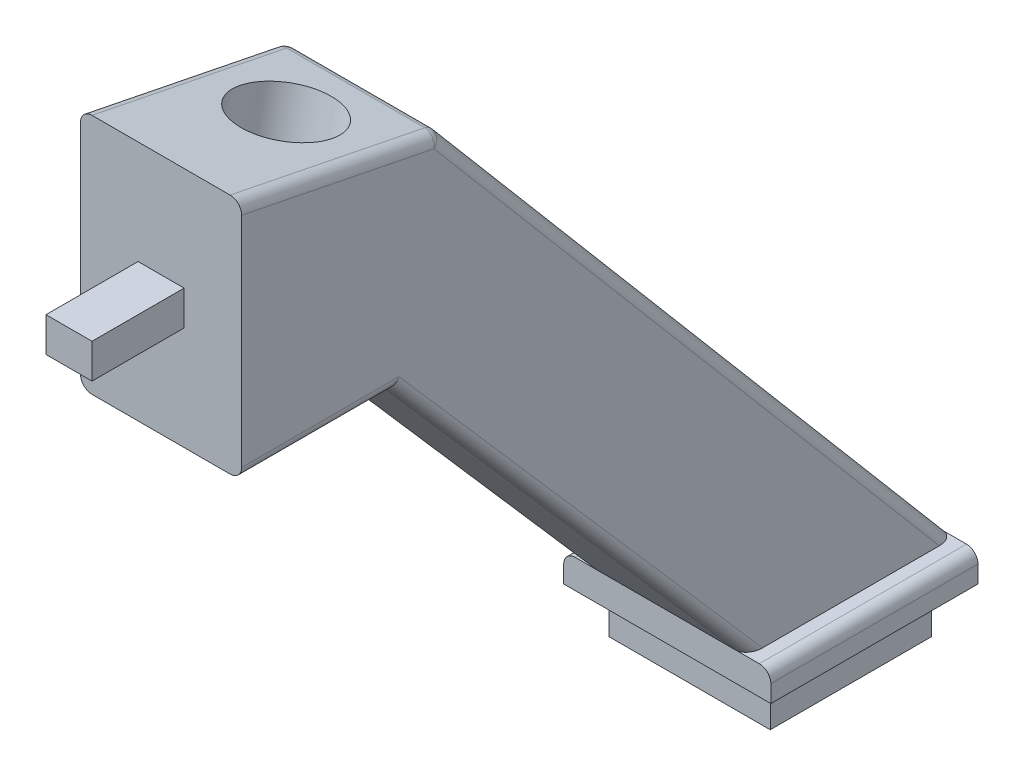
SolidWorks part; units mm, degrees
ref_plane "Front Plane" through (0, 0, 0) normal (0, 0, 1) x (1, 0, 0)
ref_plane "Top Plane" through (0, 0, 0) normal (0, 1, 0) x (1, 0, 0)
ref_plane "Right Plane" through (0, 0, 0) normal (1, 0, 0) x (0, 0, -1)
sketch "Sketch2" plane through (0, 0, 0) normal (0, 1, 0) x (1, 0, 0)
  line L2 (7, 7) -> (-7, 7)
  line L3 (-7, 7) -> (-7, -7)
  line L4 (-7, -7) -> (7, -7)
  line L5 (7, -7) -> (7, 7)
  point P4 (0, 0)
  point P8 (0, 0)
  point P11 (0, 7)
extrude "Boss-Extrude1" add sketch "Sketch2" against normal blind 4 and the other way blind 2.5
sketch "Sketch7" plane through (0, 0, 0) normal (0, 0, 1) x (1, 0, 0)
  line L0 (-6.0346, 0) -> (-4.0346, 0)
  line L2 (0, -33.0044) -> (0, 33.0044) construction
  line L3 (-6.0346, 0) -> (-6.0346, -0.5)
  line L8 (-6.0346, -0.5) -> (-4.0346, -0.5)
  line L9 (-4.0346, -0.5) -> (-4.0346, 0)
  line L10 (4.0346, -0.5) -> (4.0346, 0)
  line L11 (6.0346, -0.5) -> (4.0346, -0.5)
  line L12 (6.0346, 0) -> (6.0346, -0.5)
  line L13 (6.0346, 0) -> (4.0346, 0)
  dimension "D1" = 2
  dimension "D2" = 0.5
sketch "Sketch11" plane through (0, 0, 0) normal (0, 1, 0) x (1, 0, 0)
  line L0 (-8.9488, -8.9993) -> (-8.9488, 9.0007)
  line L1 (-8.9488, 9.0007) -> (9.0512, 9.0007)
  line L2 (-8.9488, -8.9993) -> (9.0512, -8.9993)
  line L3 (9.0512, -8.9993) -> (9.0512, 9.0007)
  dimension "D1" = 18
  dimension "D2" = 18
extrude "Boss-Extrude4" add sketch "Sketch11" along normal blind 2.5
sketch "Sketch3" plane through (0, 0, 0) normal (0, 1, 0) x (1, 0, 0)
  line L0 (2.98, 3.0412) -> (2.98, -2.9588)
  line L2 (2.98, 3.0412) -> (-3.02, 3.0412)
  line L3 (-3.02, 3.0412) -> (-3.02, -2.9588)
  line L4 (-3.02, -2.9588) -> (2.98, -2.9588)
  dimension "D1" = 6
  dimension "D2" = 6
extrude "Cut-Extrude5" cut sketch "Sketch3" against normal blind 4 and the other way blind 4
sketch "Sketch13" plane through (0, 0, 0) normal (1, 0, 0) x (0, 0, -1)
  line L1 (-39.7149, 37.7068) -> (-52.9339, 37.7068)
  line L2 (0, 0) -> (0, 2.5)
  line L3 (0, 2.5) -> (-9, 2.5)
  line L4 (0, 2.5) -> (9, 2.5)
  line L5 (-9, 2.5) -> (-39.7149, 37.7068)
  line L6 (-35.6901, 55.251) -> (9, 2.5)
  line L9 (-52.9339, 37.7068) -> (-52.9339, 58.7068)
  line L10 (-52.9339, 58.7068) -> (-35.6901, 55.251)
  point P3 (-39.7149, 37.7068)
  point P4 (-35.6901, 55.251)
  dimension "D1" = 18
  dimension "D2" = 21
extrude "Boss-Extrude5" add sketch "Sketch13" along normal blind 7 and the other way blind 7 contours L3 L5 L1 L9 L10 L6 L4
sketch "Sketch16" plane through (0, 0, 0) normal (1, 0, 0) x (0, 0, -1)
  line L0 (0, 0) -> (0.0003, 2.5)
  line L1 (-7, 0) -> (7, 0) construction
  line L2 (-8.9993, 2.5) -> (9, 2.5) construction
  line L3 (0.0003, 2.5) -> (3.0014, 2.5)
  line L4 (0.0003, 2.5) -> (-2.9997, 2.5)
  line L5 (-2.9997, 2.5) -> (-42.3379, 42.4659)
  line L6 (-42.3379, 42.4659) -> (-42.3379, 48.4659)
  line L7 (-42.3379, 48.4659) -> (3.0014, 2.5)
  dimension "D1" = 3
  dimension "D2" = 3.0011
  dimension "D3" = 6
extrude "Cut-Extrude8" cut sketch "Sketch16" against normal blind 3 and the other way blind 3 contours L4 L5 L6 L7 L3
sketch "Sketch52" plane through (0, 0, 0) normal (1, 0, 0) x (0, 0, -1)
  line L0 (-41.0385, 61.3626) -> (-48.8166, 24.8846)
sweep "Cut-Sweep4" cut path "Sketch52" circular profile diameter 8 parameters "D3"=8
fillet "Fillet1" radius 1 11 edges at (7, 20.1034, 24.3575) (-8.9488, 2.5, -0.0007) (9.0512, 2.5, -0.0007) (-7, 28.8755, 13.3451) (7, 37.7068, 46.3244) (-7, 37.7068, 46.3244) (-7, 20.1034, 24.3575) (7, 28.8755, 13.3451) (7, 56.9789, 44.312) (-7, 56.9789, 44.312) (0, 55.251, 35.6901)
sketch "Sketch59" plane through (0, 0, 0) normal (1, 0, 0) x (0, 0, -1)
  line L0 (-52.9339, 48.2068) -> (-52.9339, 49.7068)
  line L1 (-52.9339, 37.7068) -> (-52.9339, 58.7068) construction
  line L2 (-52.9339, 48.2068) -> (-52.9339, 46.7068)
  line L3 (-52.9339, 49.7068) -> (-60.9339, 49.7068)
  line L4 (-60.9339, 49.7068) -> (-60.9339, 46.7068)
  line L5 (-60.9339, 46.7068) -> (-52.9339, 46.7068)
  point P4 (-52.9339, 48.2068)
  dimension "D1" = 3
  dimension "D2" = 8
  dimension "D3" = 1.5
  dimension "D4" = 9
extrude "Boss-Extrude6" add sketch "Sketch59" along normal blind 2 and the other way blind 2 separate body
